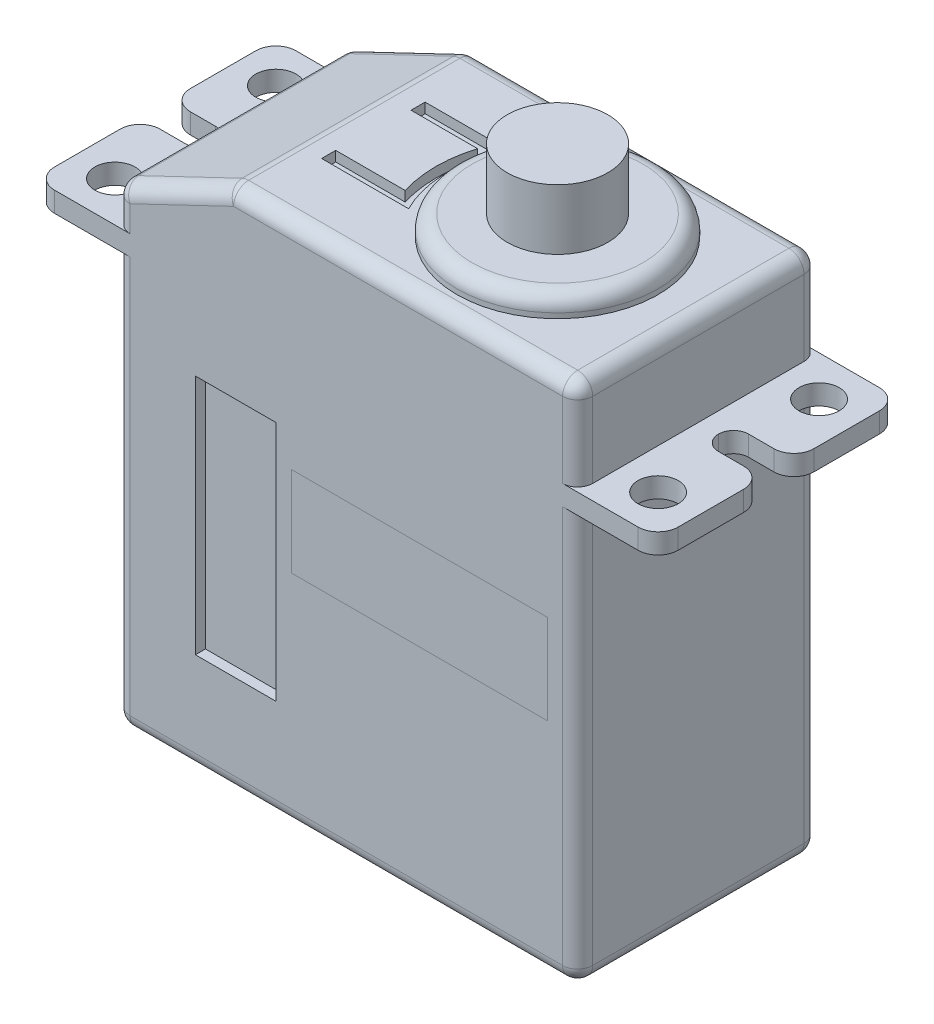
SolidWorks part; units mm, degrees
ref_plane "Front Plane" through (0, 0, 0) normal (0, 0, 1) x (1, 0, 0)
ref_plane "Top Plane" through (0, 0, 0) normal (0, 1, 0) x (1, 0, 0)
ref_plane "Right Plane" through (0, 0, 0) normal (1, 0, 0) x (0, 0, -1)
sketch "Sketch1" plane through (0, 0, 0) normal (0, 0, 1) x (1, 0, 0)
  line L1 (0, 0) -> (23, 0)
  line L2 (0, 0) -> (0, 26)
  line L3 (0, 26) -> (23, 26)
  line L4 (23, 0) -> (23, 26)
  dimension "D1" = 26
  dimension "D2" = 23
extrude "Boss-Extrude1" add sketch "Sketch1" along normal blind 12
sketch "Sketch2" plane through (0, 0, 12) normal (0, 0, 1) x (1, 0, 0)
  line L0 (5.726, 26) -> (0, 23.2609)
  line L1 (23, 26) -> (0, 26) construction
  line L2 (0, 26) -> (0, 0) construction
  line L3 (0, 23.2609) -> (0, 26)
  line L4 (0, 26) -> (5.726, 26)
extrude "Cut-Extrude1" cut sketch "Sketch2" against normal blind 12
sketch "Sketch3" plane through (0, 0, 0) normal (-1, 0, 0) x (0, 0, 1)
  line L0 (0, 23.2609) -> (0, 0) construction
  line L1 (0, 21.5) -> (12, 21.5)
  line L2 (0, 21.5) -> (0, 20.5)
  line L3 (0, 20.5) -> (12, 20.5)
  line L4 (12, 21.5) -> (12, 20.5)
  line L5 (12, 23.2609) -> (12, 0) construction
  line L6 (12, 0) -> (0, 0) construction
  dimension "D1" = 1
  dimension "D2" = 20.5
extrude "Boss-Extrude2" add sketch "Sketch3" along normal blind 4 and the other way blind 27
sketch "Sketch5" plane through (0, 21.5, 0) normal (0, 1, 0) x (1, 0, 0)
  line L0 (0, 0) -> (-4, 0) construction
  line L1 (27, 0) -> (23, 0) construction
  line L2 (0, -12) -> (-4, -12) construction
  line L3 (27, -12) -> (23, -12) construction
  circle A0 centre (-2, -10) radius 1
  circle A1 centre (-2, -2) radius 1
  circle A2 centre (25, -2) radius 1
  circle A3 centre (25, -10) radius 1
  point P10 (-2, 0)
  point P13 (25, 0)
  dimension "D5" = 2
  dimension "D1" = 2
  dimension "D2" = 2
  dimension "D3" = 2
  dimension "D4" = 2
extrude "Cut-Extrude2" cut sketch "Sketch5" against normal blind 5
sketch "Sketch6" plane through (0, 21.5, 0) normal (0, 1, 0) x (1, 0, 0)
  line L0 (-4, -12) -> (-4, 0) construction
  line L1 (-4, -5.25) -> (-1, -5.25)
  line L2 (-4, -5.25) -> (-4, -6.75)
  line L3 (-4, -6.75) -> (-1, -6.75)
  line L4 (-1, -5.25) -> (-1, -6.75)
  line L5 (27, -12) -> (27, 0) construction
  line L6 (27, -5.25) -> (24, -5.25)
  line L7 (27, -5.25) -> (27, -6.75)
  line L8 (27, -6.75) -> (24, -6.75)
  line L9 (24, -5.25) -> (24, -6.75)
  point P12 (-4, -6)
  point P13 (-1, -6)
  point P14 (27, -6)
  point P15 (24, -6)
  dimension "D1" = 1.5
  dimension "D2" = 1.5
  dimension "D3" = 3
  dimension "D4" = 3
extrude "Cut-Extrude3" cut sketch "Sketch6" against normal blind 5
fillet "Fillet1" radius 1 8 edges at (-4, 21, 5.25) (27, 21, 0) (27, 21, 5.25) (27, 21, 6.75) (27, 21, 12) (-4, 21, 12) (-4, 21, 6.75) (-4, 21, 0)
fillet "Fillet2" radius 0.75 4 edges at (-1, 21, 6.75) (-1, 21, 5.25) (24, 21, 6.75) (24, 21, 5.25)
sketch "Sketch7" plane through (0, 26, 0) normal (0, 1, 0) x (1, 0, 0)
  line L0 (23, -12) -> (23, 0) construction
  line L1 (23, -12) -> (23, 0) construction
  circle A0 centre (16, -6) radius 5
  point P4 (23, -6)
  dimension "D1" = 10
  dimension "D2" = 7
extrude "Boss-Extrude3" add sketch "Sketch7" along normal blind 1
sketch "Sketch8" plane through (0, 26, 0) normal (0, 1, 0) x (1, 0, 0)
  line L0 (11.1019, -3.5) -> (6.9174, -3.5)
  line L1 (6.9174, -3.5) -> (6.9174, -4.2)
  line L2 (6.9174, -4.2) -> (10.2291, -4.2)
  line L3 (6.7735, -8.5) -> (11.1019, -8.5)
  line L4 (6.7735, -8.5) -> (6.7735, -7.8)
  line L5 (6.7735, -7.8) -> (10.2291, -7.8)
  line L6 (23, 0) -> (5.726, 0) construction
  line L7 (23, -12) -> (5.726, -12) construction
  arc A0 (11.1019, -3.5) -> (11.1019, -8.5) centre (16, -6) ccw
  arc A1 (10.2291, -4.2) -> (10.2291, -7.8) centre (16, -6) ccw
  dimension "D1" = 0.7
  dimension "D2" = 0.7
  dimension "D3" = 3.5
  dimension "D4" = 3.5
extrude "Cut-Extrude4" cut sketch "Sketch8" against normal blind 0.5
fillet "Fillet3" radius 0.75 20 edges at (23, 0, 6) (11.5, 0, 12) (0, 0, 6) (0, 22.3805, 0) (0, 22.3805, 12) (0, 10.25, 12) (0, 10.25, 0) (11.5, 0, 0) (23, 26, 6) (23, 23.75, 12) (23, 10.25, 12) (23, 10.25, 0) (23, 23.75, 0) (16, 27, 11) (14.363, 26, 12) (2.863, 24.6305, 12) (0, 23.2609, 6) (2.863, 24.6305, 0) (5.726, 26, 6) (14.363, 26, 0)
sketch "Sketch9" plane through (0, 0, 12) normal (0, 0, 1) x (1, 0, 0)
  line L0 (22.25, 0) -> (0.75, 0) construction
  line L1 (4, 17) -> (8, 17)
  line L2 (4, 17) -> (4, 5)
  line L3 (4, 5) -> (8, 5)
  line L4 (8, 17) -> (8, 5)
  line L5 (0, 0.75) -> (0, 20.5) construction
  dimension "D1" = 12
  dimension "D2" = 4
  dimension "D3" = 5
  dimension "D4" = 4
extrude "Cut-Extrude5" cut sketch "Sketch9" against normal blind 0.5
sketch "Sketch10" plane through (0, 27, 0) normal (0, 1, 0) x (1, 0, 0)
  circle A0 centre (16, -6) radius 2.5
  dimension "D1" = 5
extrude "Boss-Extrude4" add sketch "Sketch10" along normal blind 3
sketch "Sketch11" plane through (0, 0, 12) normal (0, 0, 1) x (1, 0, 0)
  line L1 (8.7709, 15.3612) -> (21.4934, 15.3612)
  line L2 (8.7709, 15.3612) -> (8.7709, 10.9063)
  line L3 (8.7709, 10.9063) -> (21.4934, 10.9063)
  line L4 (21.4934, 15.3612) -> (21.4934, 10.9063)
split line "Split Line1"
sketch "Sketch13" plane through (0, 0, 0) normal (0, 0, -1) x (-1, 0, 0)
sketch "Sketch14" plane through (0, 0, 0) normal (0, -1, 0) x (1, 0, 0)
sketch "Sketch15" plane through (0, 26, 0) normal (0, 1, 0) x (1, 0, 0)
ref_plane "Plane1" through (6.9174, 26, 4.2) normal (1, 0, 0) x (0, 0, -1)
sketch "Sketch17" plane through (0, 26, 0) normal (0, 1, 0) x (1, 0, 0)
  line L0 (5.8962, 0) -> (22.25, 0) construction
  line L1 (22.25, -12) -> (5.8962, -12) construction
